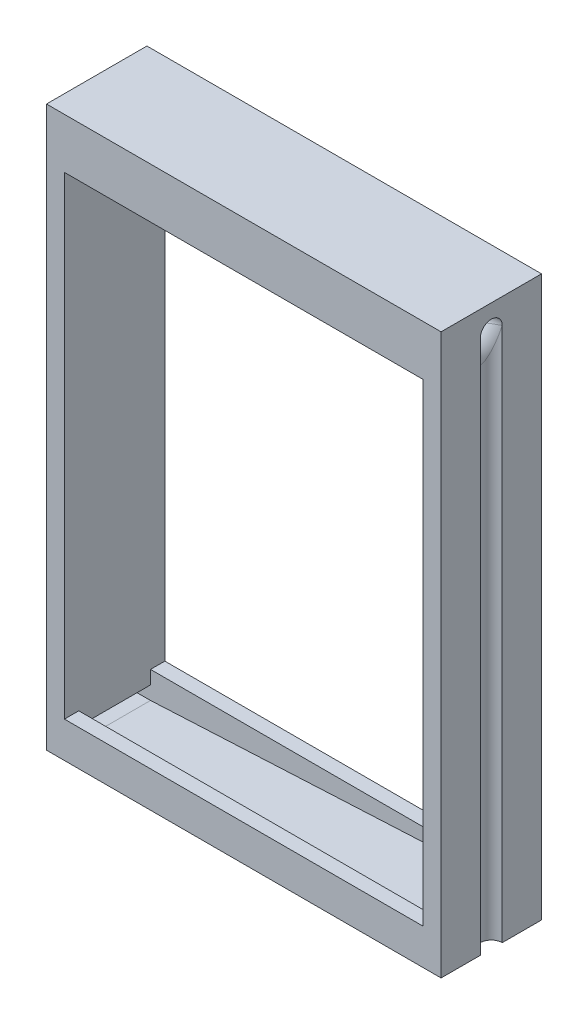
SolidWorks part; units mm, degrees
other "Marca1"
sketch "Croquis8" plane through (110, 156, 0) normal (0.9773, 0.2107, 0.0228) x (0.1072, -0.3985, -0.9109)
ref_plane "Front Plane" through (0, 0, 0) normal (0, 0, 1) x (1, 0, 0)
ref_plane "Top Plane" through (0, 0, 0) normal (0, 1, 0) x (1, 0, 0)
ref_plane "Right Plane" through (0, 0, 0) normal (1, 0, 0) x (0, 0, -1)
sketch "Croquis1" plane through (0, 0, 0) normal (0, 0, 1) x (1, 0, 0)
  line L1 (0, 0) -> (110, 0)
  line L2 (0, 0) -> (0, 156)
  line L3 (0, 156) -> (110, 156)
  line L4 (110, 0) -> (110, 156)
  line L5 (5, 10) -> (105, 10)
  line L6 (5, 10) -> (5, 142)
  line L7 (5, 142) -> (105, 142)
  line L8 (105, 10) -> (105, 142)
  dimension "D1" = 132
  dimension "D2" = 110
  dimension "D3" = 14
  dimension "D4" = 10
  dimension "D5" = 5
  dimension "D6" = 100
extrude "Saliente-Extruir2" add sketch "Croquis1" against normal blind 28
ref_plane "Plano1" through (0, 0, -14) normal (0, 0, 1) x (1, 0, 0)
sketch "Croquis3" plane through (0, 0, -14) normal (0, 0, 1) x (1, 0, 0)
  line L0 (5, 10) -> (5, 0) construction
  line L1 (0, 0) -> (110, 0) construction
  line L2 (5, 2.5) -> (105, 7.5)
  line L4 (5, 7.5) -> (5, 2.5)
  line L5 (105, 7.5) -> (105, 10)
  line L6 (105, 10) -> (5, 10)
  line L7 (5, 10) -> (5, 7.5)
  dimension "D1" = 5
  dimension "D2" = 2.5
  dimension "D3" = 2.5
extrude "Cortar-Extruir1" cut sketch "Croquis3" against normal mid plane 20
sketch "Croquis4" plane through (5, 0, 0) normal (1, 0, 0) x (0, 0, -1)
  line L0 (24, 10) -> (24, 2.5) construction
  line L1 (4, 2.5) -> (24, 2.5)
  line L2 (4, 2.5) -> (4, 6.25)
  line L3 (4, 6.25) -> (24, 6.25)
  line L4 (24, 2.5) -> (24, 6.25)
extrude "Cortar-Extruir2" cut sketch "Croquis4" against normal through all
sketch "Croquis6" plane through (110, 0, 0) normal (1, 0, 0) x (0, 0, -1)
  line L0 (28, 142) -> (0, 142) construction
  line L1 (28, 142) -> (0, 142) construction
  line L2 (14, 142) -> (14, 156) construction
  line L3 (28, 156) -> (0, 156) construction
  circle A0 centre (14, 149) radius 3.05
  dimension "D1" = 6.1
extrude "Cortar-Extruir3" cut sketch "Croquis6" against normal up to surface (105 mm away) up to face at (5, 42.0625, -14)
sketch "Croquis7" plane through (0, 142, 0) normal (0, -1, 0) x (1, 0, 0)
  line L0 (5, -14) -> (105, -14) construction
  line L1 (5, -28) -> (5, 0) construction
  line L2 (105, -28) -> (105, 0) construction
  line L3 (5, -16.5) -> (105, -16.5)
  line L4 (5, -11.5) -> (105, -11.5)
  line L5 (5, -11.5) -> (5, -16.5)
  line L6 (105, -16.5) -> (105, -11.5)
  dimension "D1" = 2.5
  dimension "D2" = 2.5
extrude "Cortar-Extruir4" cut sketch "Croquis7" against normal up to next
sketch "Croquis11" plane through (0, 0, 0) normal (0, -1, 0) x (1, 0, 0)
  line L0 (110, -28) -> (110, 0) construction
  line L1 (110, -17.05) -> (110, -10.95)
  arc A0 (110, -17.05) -> (110, -10.95) centre (110, -14) cw
  dimension "D1" = 3.05
extrude "Cortar-Extruir5" cut sketch "Croquis11" against normal up to next
fillet "Redondeo1" radius 6.5 1 edges at (106.95, 145.95, -14)
